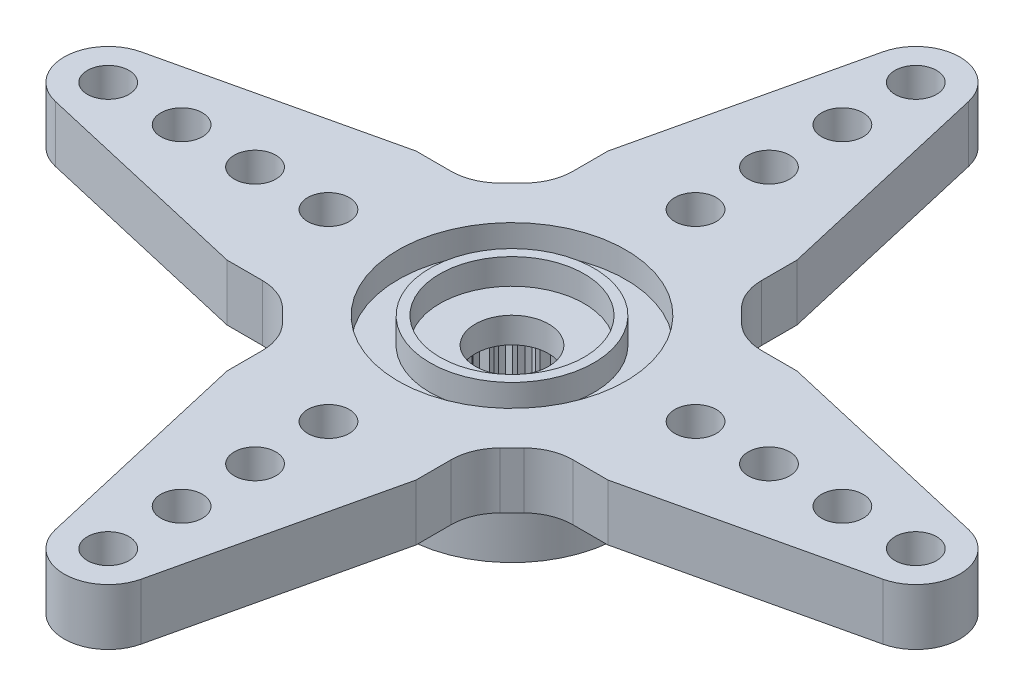
SolidWorks part; units mm, degrees
material "PA Type 6"
ref_plane "Plan de face" through (0, 0, 0) normal (0, 0, 1) x (1, 0, 0)
ref_plane "Plan de dessus" through (0, 0, 0) normal (0, 1, 0) x (1, 0, 0)
ref_plane "Plan de droite" through (0, 0, 0) normal (1, 0, 0) x (0, 0, -1)
ref_axis "Axe1" through (0, 0, 0) along (0, 1, 0)
sketch "Esquisse1" plane through (0, 0, 0) normal (0, 1, 0) x (1, 0, 0)
  line L0 (-18.3, 0) -> (18.3, 0) construction
  line L1 (0, 0) -> (0, -8.9896) construction
  line L2 (-16.9049, 1.7539) -> (-7.7822, 3.86)
  line L3 (-16.9049, -1.7539) -> (-7.7822, -3.86)
  line L4 (0, 0) -> (-4.6881, 4.6881) construction
  line L5 (-4.6881, 4.6881) -> (-4.9304, 4.4458)
  line L6 (-4.6881, 4.6881) -> (0, 4.6881)
  line L7 (-4.6881, -4.6881) -> (0, -4.6881)
  line L8 (-4.6881, -4.6881) -> (-4.9304, -4.4458)
  line L9 (-6.3447, 3.86) -> (-7.7822, 3.86)
  line L10 (-6.3447, -3.86) -> (-7.7822, -3.86)
  circle A0 centre (0, 0) radius 18.3 construction
  arc A2 (-16.9049, 1.7539) -> (-16.9049, -1.7539) centre (-16.5, 0) ccw
  circle A3 centre (-16.5, 0) radius 0.85
  circle A4 centre (-13.5, 0) radius 0.85
  circle A5 centre (-10.5, 0) radius 0.85
  circle A6 centre (-7.5, 0) radius 0.85
  arc A7 (-6.3447, 3.86) -> (-4.9304, 4.4458) centre (-6.3447, 5.86) ccw
  arc A8 (-6.3447, -3.86) -> (-4.9304, -4.4458) centre (-6.3447, -5.86) cw
  circle A12 centre (0, 0) radius 4.65
  circle A13 centre (0, 0) radius 1.5
  circle A14 centre (0, 0) radius 3.35
  circle A15 centre (0, 0) radius 2.95
  dimension "D1" = 36.6
  dimension "D3" = 1.7
  dimension "D9" = 9.3
  dimension "D10" = 6.7
  dimension "D11" = 0.4
  dimension "D12" = 3
  dimension "D15" = 2
  dimension "D8" = 6.63
  dimension "D4" = 3
  dimension "D5" = 3
  dimension "D6" = 3
  dimension "D7" = 33
  dimension "D13" = 45
  dimension "D14" = 7.72
  dimension "D16" = 26
sketch "Esquisse2" plane through (0, 0, 0) normal (0, 0, 1) x (1, 0, 0)
  line L0 (0, 3.9296) -> (0, -5.2174) construction
  line L1 (21.01, 0) -> (-21.01, 0) construction
  line L2 (0, -3.5) -> (-4.45, -3.5)
  line L3 (0, -3.5) -> (0, 2.1)
  line L4 (0, 2.1) -> (-4.45, 2.1)
  line L5 (-4.45, -3.5) -> (-4.45, 2.1)
  point P9 (-4.45, -0.2)
  dimension "D1" = 8.9
  dimension "D2" = 3.5
  dimension "D3" = 3.3
  dimension "D4" = 2.3
revolve "Révolution1" add sketch "Esquisse2" angle 360 about L0
sketch "Esquisse3" plane through (0, 2.1, 0) normal (0, 1, 0) x (1, 0, 0)
  line L0 (-16.9049, 1.7539) -> (-7.7822, 3.86) construction
  line L1 (-16.9049, -1.7539) -> (-7.7822, -3.86) construction
  line L2 (-16.9049, 1.7539) -> (-7.7822, 3.86)
  line L3 (-16.9049, -1.7539) -> (-7.7822, -3.86)
  line L4 (0, 0) -> (0, -8.9896) construction
  line L5 (0, 0) -> (0, -8.9896) construction
  line L6 (-6.3447, 3.86) -> (-7.7822, 3.86) construction
  line L7 (-4.6881, 4.6881) -> (-4.9304, 4.4458) construction
  line L8 (-4.6881, 4.6881) -> (0, 4.6881) construction
  line L9 (-6.3447, 3.86) -> (-7.7822, 3.86)
  line L10 (-4.6881, 4.6881) -> (-4.9304, 4.4458)
  line L11 (-4.6881, 4.6881) -> (0, 4.6881)
  line L12 (-6.3447, -3.86) -> (-7.7822, -3.86) construction
  line L13 (-4.6881, -4.6881) -> (-4.9304, -4.4458) construction
  line L14 (-4.6881, -4.6881) -> (0, -4.6881) construction
  line L15 (-6.3447, -3.86) -> (-7.7822, -3.86)
  line L16 (-4.6881, -4.6881) -> (-4.9304, -4.4458)
  line L17 (-4.6881, -4.6881) -> (0, -4.6881)
  line L18 (0, 4.6881) -> (0, -4.6881)
  arc A0 (-16.9049, 1.7539) -> (-16.9049, -1.7539) centre (-16.5, 0) ccw construction
  circle A1 centre (-16.5, 0) radius 0.85 construction
  circle A2 centre (-13.5, 0) radius 0.85 construction
  circle A3 centre (-10.5, 0) radius 0.85 construction
  circle A4 centre (-7.5, 0) radius 0.85 construction
  arc A6 (-16.9049, 1.7539) -> (-16.9049, -1.7539) centre (-16.5, 0) ccw
  circle A7 centre (-16.5, 0) radius 0.85
  circle A8 centre (-13.5, 0) radius 0.85
  circle A9 centre (-10.5, 0) radius 0.85
  circle A10 centre (-7.5, 0) radius 0.85
  arc A11 (-6.3447, 3.86) -> (-4.9304, 4.4458) centre (-6.3447, 5.86) ccw construction
  arc A12 (-6.3447, 3.86) -> (-4.9304, 4.4458) centre (-6.3447, 5.86) ccw
  arc A13 (-4.9304, -4.4458) -> (-6.3447, -3.86) centre (-6.3447, -5.86) ccw construction
  arc A14 (-4.9304, -4.4458) -> (-6.3447, -3.86) centre (-6.3447, -5.86) ccw
extrude "Boss.-Extru.1" add sketch "Esquisse3" against normal up to vertex (2.3 mm away) up to point (-4.45, -0.2, 0)
pattern_circular "Répétition circulaire2" count 4 over 360 about axis through (0, 0, 0) along (0, 1, 0) of "Boss.-Extru.1"
sketch "Esquisse4" plane through (0, 2.1, 0) normal (0, 1, 0) x (1, 0, 0)
  circle A0 centre (0, 0) radius 2.95 construction
  circle A1 centre (0, 0) radius 2.95
extrude "Enlèv. mat.-Extru.1" cut sketch "Esquisse4" against normal blind 1.05
sketch "Esquisse5" plane through (0, 2.1, 0) normal (0, 1, 0) x (1, 0, 0)
  circle A0 centre (0, 0) radius 3.35 construction
  circle A1 centre (0, 0) radius 4.65 construction
  circle A2 centre (0, 0) radius 3.35
  circle A3 centre (0, 0) radius 4.65
extrude "Enlèv. mat.-Extru.2" cut sketch "Esquisse5" against normal blind 1.05
sketch "Esquisse6" plane through (0, -3.5, 0) normal (0, -1, 0) x (1, 0, 0)
  circle A0 centre (0, 0) radius 1.5 construction
  circle A1 centre (0, 0) radius 1.5
extrude "Enlèv. mat.-Extru.3" cut sketch "Esquisse6" against normal through all
sketch "Esquisse7" plane through (0, 0, 0) normal (0, 1, 0) x (1, 0, 0)
  line L6 (0.1267, -2.9973) -> (0.2711, -2.6537)
  line L7 (0.3973, -2.6377) -> (0.6227, -2.9347)
  line L8 (0, 0) -> (0, -3.7146) construction
  line L9 (0, 0) -> (0.3388, -2.6821) construction
  arc A4 (0.1267, -2.9973) -> (0.6227, -2.9347) centre (0, 0) ccw
  arc A5 (0.3973, -2.6377) -> (0.2711, -2.6537) centre (0.3388, -2.6821) ccw
  dimension "D2" = 6
  dimension "D7" = 0.37
  dimension "D4" = 0.5
  dimension "D5" = 7.2
  dimension "D6" = 60
sketch "Esquisse8" plane through (0, 0, 0) normal (0, 1, 0) x (1, 0, 0)
  circle A0 centre (0, 0) radius 2.68
  arc A1 (0.3973, -2.6377) -> (0.2711, -2.6537) centre (0.3388, -2.6821) ccw construction
  dimension "D1" = 0.05
extrude "Enlèv. mat.-Extru.4" cut sketch "Esquisse8" against normal through all
sketch "Esquisse9" plane through (0, 0, 0) normal (0, 1, 0) x (1, 0, 0)
  line L0 (0.1267, -2.9973) -> (0.2711, -2.6537) construction
  line L2 (0.1053, -3.0482) -> (0.2656, -2.6668)
  line L3 (-0.2656, -2.6668) -> (-0.1053, -3.0482)
  line L4 (0, -2.4923) -> (0, -2.738) construction
  line L5 (0, 0) -> (0, -3.7146) construction
  arc A0 (-0.1053, -3.0482) -> (0.1053, -3.0482) centre (0, 0) ccw
  circle A1 centre (0, 0) radius 2.68
  arc A2 (-0.2656, -2.6668) -> (0.2656, -2.6668) centre (0, 0) ccw
  arc A3 (0.1267, -2.9973) -> (0.6227, -2.9347) centre (0, 0) ccw construction
  dimension "D2" = 0.05
  dimension "D1" = 0
extrude "Enlèv. mat.-Extru.5" cut sketch "Esquisse9" against normal through all
pattern_circular "Répétition circulaire1" count 25 over 360 about axis through (0, 0, 0) along (0, 1, 0) of "Enlèv. mat.-Extru.5"
